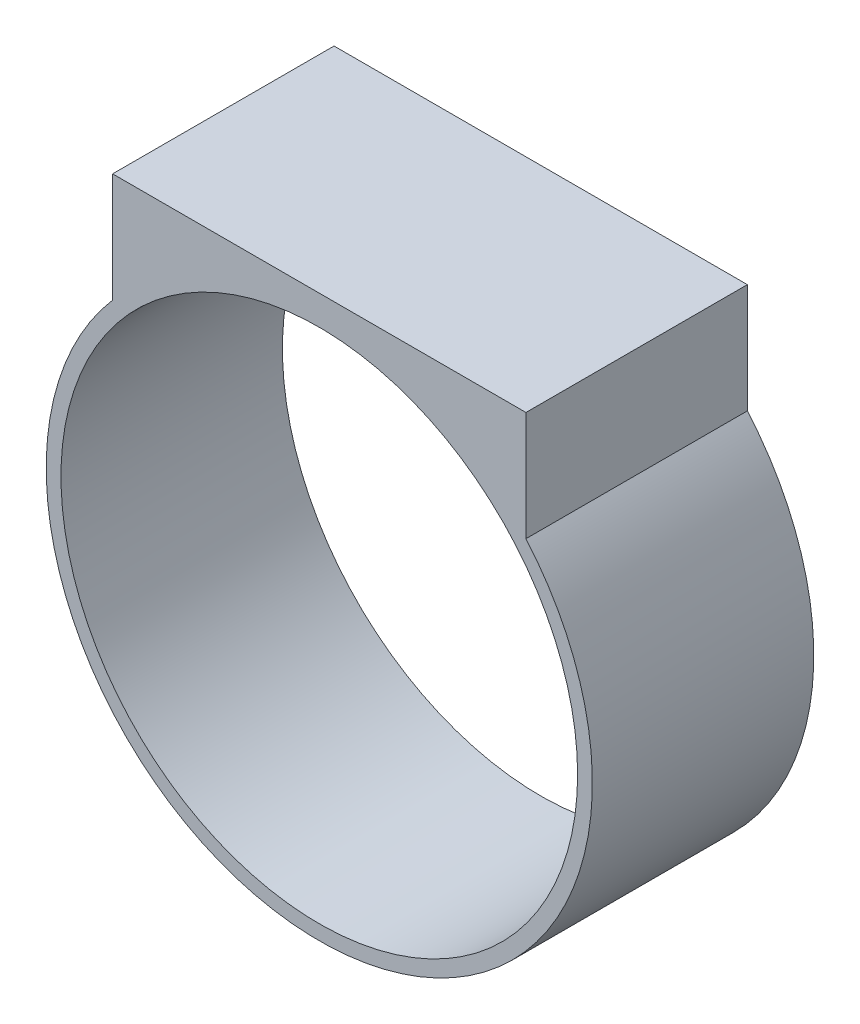
SolidWorks part; units mm, degrees
ref_plane "Front Plane" through (0, 0, 0) normal (0, 0, 1) x (1, 0, 0)
ref_plane "Top Plane" through (0, 0, 0) normal (0, 1, 0) x (1, 0, 0)
ref_plane "Right Plane" through (0, 0, 0) normal (1, 0, 0) x (0, 0, -1)
ref_plane "Plane1" through (0, 0, 0) normal (0, 0, 1) x (1, 0, 0)
sketch "Sketch3" plane through (0, 0, 0) normal (0, 0, 1) x (1, 0, 0)
  circle A0 centre (0, 0) radius 92.5
  circle A1 centre (0, 0) radius 87.5
extrude "Boss-Extrude3" add sketch "Sketch3" along normal blind 75
ref_plane "Plane4" through (0, 0, 0) normal (0, 1, 0) x (1, 0, 0)
ref_plane "Plane5" through (0, 92.5, 0) normal (0, 1, 0) x (1, 0, 0)
sketch "Sketch4" plane through (0, 92.5, 0) normal (0, 1, 0) x (1, 0, 0)
  line L0 (-89.4759, 0) -> (89.4759, 0) construction
  line L1 (-70, 0) -> (70, 0)
  line L2 (-70, 0) -> (-70, -75)
  line L3 (-70, -75) -> (70, -75)
  line L4 (70, 0) -> (70, -75)
  line L5 (-92.5, -75) -> (92.5, -75) construction
extrude "Boss-Extrude4" add sketch "Sketch4" against normal up to surface and the other way blind 5 up to face at (92.5, 0, 75)
